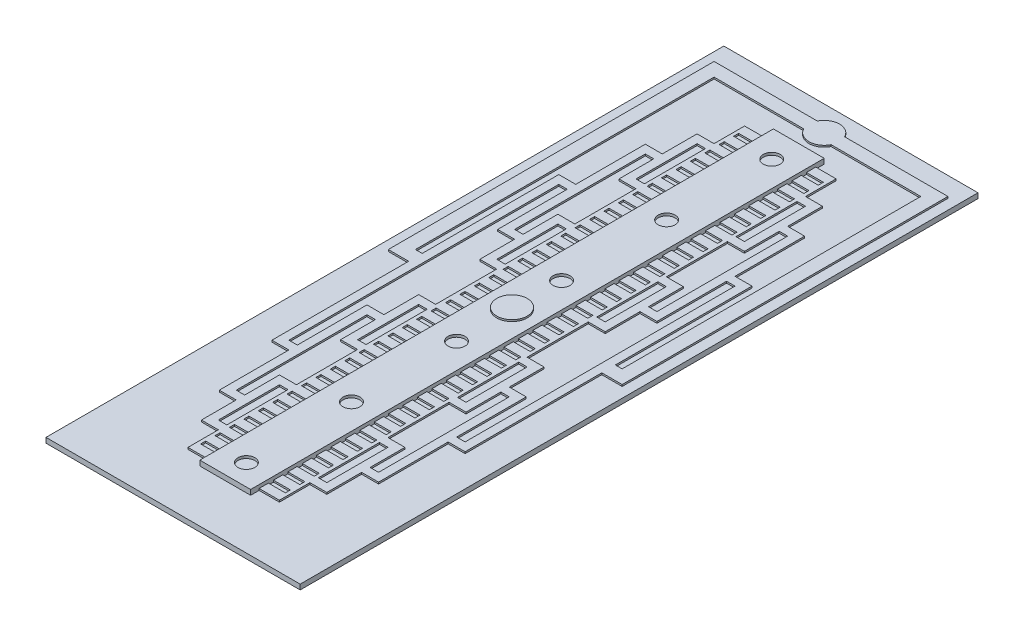
SolidWorks part; units mm, degrees
ref_plane "Front Plane" through (0, 0, 0) normal (0, 0, 1) x (1, 0, 0)
ref_plane "Top Plane" through (0, 0, 0) normal (0, 1, 0) x (1, 0, 0)
ref_plane "Right Plane" through (0, 0, 0) normal (1, 0, 0) x (0, 0, -1)
sketch "Sketch2" plane through (0, 0, 0) normal (0, 1, 0) x (1, 0, 0)
  line L1 (-7.5, 20) -> (7.5, 20)
  line L2 (-7.5, 20) -> (-7.5, -20)
  line L3 (-7.5, -20) -> (7.5, -20)
  line L4 (7.5, 20) -> (7.5, -20)
  line L5 (-7.5, 20) -> (7.5, -20) construction
  line L6 (-7.5, -20) -> (7.5, 20) construction
  point P0 (0, 0)
extrude "Boss-Extrude1" add sketch "Sketch2" along normal blind 0.3
sketch "Sketch3" plane through (0, 0.3, 0) normal (0, 1, 0) x (1, 0, 0)
  line L1 (-1.5, 16.925) -> (1.5, 16.925)
  line L2 (-1.5, 16.925) -> (-1.5, -16.925)
  line L3 (-1.5, -16.925) -> (1.5, -16.925)
  line L4 (1.5, 16.925) -> (1.5, -16.925)
  line L5 (-1.5, 16.925) -> (1.5, -16.925) construction
  line L6 (-1.5, -16.925) -> (1.5, 16.925) construction
  point P0 (0, 0)
extrude "Boss-Extrude2" add sketch "Sketch3" along normal blind 0.3
sketch "Sketch4" plane through (0, 0.3, 0) normal (0, 1, 0) x (1, 0, 0)
  line L0 (0, 19.2283) -> (0, -19.2283) construction
  line L1 (-7.7467, 0) -> (7.7467, 0) construction
  line L2 (1.5, 16.425) -> (2.7, 16.425)
  line L3 (1.5, 16.425) -> (1.5, -16.425)
  line L4 (2.7, 16.425) -> (2.7, -16.425)
  line L5 (1.5, -16.425) -> (2.7, -16.425)
  line L6 (1.5, -16.925) -> (1.5, 16.925) construction
  line L7 (-1.5, -16.425) -> (-2.7, -16.425)
  line L8 (-1.5, 16.425) -> (-1.5, -16.425)
  line L9 (-2.7, 16.425) -> (-2.7, -16.425)
  line L10 (-1.5, 16.425) -> (-2.7, 16.425)
  point P3 (2.7, 0)
  point P4 (0, 0)
  point P8 (0, 0)
extrude "Boss-Extrude3" add sketch "Sketch4" along normal blind 0.1
sketch "Sketch5" plane through (0, 0.4, 0) normal (0, 1, 0) x (1, 0, 0)
  line L0 (1.5, 16.425) -> (1.5, -16.425) construction
  line L1 (1.5, 15.875) -> (2.5, 15.875)
  line L2 (1.5, 15.875) -> (1.5, 15.575)
  line L3 (2.5, 15.875) -> (2.5, 15.575)
  line L4 (1.5, 15.575) -> (2.5, 15.575)
  line L5 (-1.5, 15.875) -> (-1.5, 15.575)
  line L6 (-2.5, 15.875) -> (-1.5, 15.875)
  line L7 (-2.5, 15.875) -> (-2.5, 15.575)
  line L8 (-2.5, 15.575) -> (-1.5, 15.575)
  line L9 (-1.5, 15.025) -> (-1.5, 14.725)
  line L10 (-2.5, 15.025) -> (-1.5, 15.025)
  line L11 (-2.5, 15.025) -> (-2.5, 14.725)
  line L12 (-2.5, 14.725) -> (-1.5, 14.725)
  line L13 (-1.5, 14.175) -> (-1.5, 13.875)
  line L14 (-2.5, 14.175) -> (-1.5, 14.175)
  line L15 (-2.5, 14.175) -> (-2.5, 13.875)
  line L16 (-2.5, 13.875) -> (-1.5, 13.875)
  line L17 (-1.5, 13.325) -> (-1.5, 13.025)
  line L18 (-2.5, 13.325) -> (-1.5, 13.325)
  line L19 (-2.5, 13.325) -> (-2.5, 13.025)
  line L20 (-2.5, 13.025) -> (-1.5, 13.025)
  line L21 (-1.5, 12.475) -> (-1.5, 12.175)
  line L22 (-2.5, 12.475) -> (-1.5, 12.475)
  line L23 (-2.5, 12.475) -> (-2.5, 12.175)
  line L24 (-2.5, 12.175) -> (-1.5, 12.175)
  line L25 (-1.5, 11.625) -> (-1.5, 11.325)
  line L26 (-2.5, 11.625) -> (-1.5, 11.625)
  line L27 (-2.5, 11.625) -> (-2.5, 11.325)
  line L28 (-2.5, 11.325) -> (-1.5, 11.325)
  line L29 (-1.5, 10.775) -> (-1.5, 10.475)
  line L30 (-2.5, 10.775) -> (-1.5, 10.775)
  line L31 (-2.5, 10.775) -> (-2.5, 10.475)
  line L32 (-2.5, 10.475) -> (-1.5, 10.475)
  line L33 (-1.5, 9.925) -> (-1.5, 9.625)
  line L34 (-2.5, 9.925) -> (-1.5, 9.925)
  line L35 (-2.5, 9.925) -> (-2.5, 9.625)
  line L36 (-2.5, 9.625) -> (-1.5, 9.625)
  line L37 (-1.5, 9.075) -> (-1.5, 8.775)
  line L38 (-2.5, 9.075) -> (-1.5, 9.075)
  line L39 (-2.5, 9.075) -> (-2.5, 8.775)
  line L40 (-2.5, 8.775) -> (-1.5, 8.775)
  line L41 (-1.5, 8.225) -> (-1.5, 7.925)
  line L42 (-2.5, 8.225) -> (-1.5, 8.225)
  line L43 (-2.5, 8.225) -> (-2.5, 7.925)
  line L44 (-2.5, 7.925) -> (-1.5, 7.925)
  line L45 (-1.5, 7.375) -> (-1.5, 7.075)
  line L46 (-2.5, 7.375) -> (-1.5, 7.375)
  line L47 (-2.5, 7.375) -> (-2.5, 7.075)
  line L48 (-2.5, 7.075) -> (-1.5, 7.075)
  line L49 (-1.5, 6.525) -> (-1.5, 6.225)
  line L50 (-2.5, 6.525) -> (-1.5, 6.525)
  line L51 (-2.5, 6.525) -> (-2.5, 6.225)
  line L52 (-2.5, 6.225) -> (-1.5, 6.225)
  line L53 (-1.5, 5.675) -> (-1.5, 5.375)
  line L54 (-2.5, 5.675) -> (-1.5, 5.675)
  line L55 (-2.5, 5.675) -> (-2.5, 5.375)
  line L56 (-2.5, 5.375) -> (-1.5, 5.375)
  line L57 (-1.5, 4.825) -> (-1.5, 4.525)
  line L58 (-2.5, 4.825) -> (-1.5, 4.825)
  line L59 (-2.5, 4.825) -> (-2.5, 4.525)
  line L60 (-2.5, 4.525) -> (-1.5, 4.525)
  line L61 (-1.5, 3.975) -> (-1.5, 3.675)
  line L62 (-2.5, 3.975) -> (-1.5, 3.975)
  line L63 (-2.5, 3.975) -> (-2.5, 3.675)
  line L64 (-2.5, 3.675) -> (-1.5, 3.675)
  line L65 (-1.5, 3.125) -> (-1.5, 2.825)
  line L66 (-2.5, 3.125) -> (-1.5, 3.125)
  line L67 (-2.5, 3.125) -> (-2.5, 2.825)
  line L68 (-2.5, 2.825) -> (-1.5, 2.825)
  line L69 (-1.5, 2.275) -> (-1.5, 1.975)
  line L70 (-2.5, 2.275) -> (-1.5, 2.275)
  line L71 (-2.5, 2.275) -> (-2.5, 1.975)
  line L72 (-2.5, 1.975) -> (-1.5, 1.975)
  line L73 (-1.5, 1.425) -> (-1.5, 1.125)
  line L74 (-2.5, 1.425) -> (-1.5, 1.425)
  line L75 (-2.5, 1.425) -> (-2.5, 1.125)
  line L76 (-2.5, 1.125) -> (-1.5, 1.125)
  line L77 (-1.5, 0.575) -> (-1.5, 0.275)
  line L78 (-2.5, 0.575) -> (-1.5, 0.575)
  line L79 (-2.5, 0.575) -> (-2.5, 0.275)
  line L80 (-2.5, 0.275) -> (-1.5, 0.275)
  line L81 (-1.5, -0.275) -> (-1.5, -0.575)
  line L82 (-2.5, -0.275) -> (-1.5, -0.275)
  line L83 (-2.5, -0.275) -> (-2.5, -0.575)
  line L84 (-2.5, -0.575) -> (-1.5, -0.575)
  line L85 (-1.5, -1.125) -> (-1.5, -1.425)
  line L86 (-2.5, -1.125) -> (-1.5, -1.125)
  line L87 (-2.5, -1.125) -> (-2.5, -1.425)
  line L88 (-2.5, -1.425) -> (-1.5, -1.425)
  line L89 (-1.5, -1.975) -> (-1.5, -2.275)
  line L90 (-2.5, -1.975) -> (-1.5, -1.975)
  line L91 (-2.5, -1.975) -> (-2.5, -2.275)
  line L92 (-2.5, -2.275) -> (-1.5, -2.275)
  line L93 (-1.5, -2.825) -> (-1.5, -3.125)
  line L94 (-2.5, -2.825) -> (-1.5, -2.825)
  line L95 (-2.5, -2.825) -> (-2.5, -3.125)
  line L96 (-2.5, -3.125) -> (-1.5, -3.125)
  line L97 (-1.5, -3.675) -> (-1.5, -3.975)
  line L98 (-2.5, -3.675) -> (-1.5, -3.675)
  line L99 (-2.5, -3.675) -> (-2.5, -3.975)
  line L100 (-2.5, -3.975) -> (-1.5, -3.975)
  line L101 (-1.5, -4.525) -> (-1.5, -4.825)
  line L102 (-2.5, -4.525) -> (-1.5, -4.525)
  line L103 (-2.5, -4.525) -> (-2.5, -4.825)
  line L104 (-2.5, -4.825) -> (-1.5, -4.825)
  line L105 (-1.5, -5.375) -> (-1.5, -5.675)
  line L106 (-2.5, -5.375) -> (-1.5, -5.375)
  line L107 (-2.5, -5.375) -> (-2.5, -5.675)
  line L108 (-2.5, -5.675) -> (-1.5, -5.675)
  line L109 (-1.5, -6.225) -> (-1.5, -6.525)
  line L110 (-2.5, -6.225) -> (-1.5, -6.225)
  line L111 (-2.5, -6.225) -> (-2.5, -6.525)
  line L112 (-2.5, -6.525) -> (-1.5, -6.525)
  line L113 (-1.5, -7.075) -> (-1.5, -7.375)
  line L114 (-2.5, -7.075) -> (-1.5, -7.075)
  line L115 (-2.5, -7.075) -> (-2.5, -7.375)
  line L116 (-2.5, -7.375) -> (-1.5, -7.375)
  line L117 (-1.5, -7.925) -> (-1.5, -8.225)
  line L118 (-2.5, -7.925) -> (-1.5, -7.925)
  line L119 (-2.5, -7.925) -> (-2.5, -8.225)
  line L120 (-2.5, -8.225) -> (-1.5, -8.225)
  line L121 (-1.5, -8.775) -> (-1.5, -9.075)
  line L122 (-2.5, -8.775) -> (-1.5, -8.775)
  line L123 (-2.5, -8.775) -> (-2.5, -9.075)
  line L124 (-2.5, -9.075) -> (-1.5, -9.075)
  line L125 (-1.5, -9.625) -> (-1.5, -9.925)
  line L126 (-2.5, -9.625) -> (-1.5, -9.625)
  line L127 (-2.5, -9.625) -> (-2.5, -9.925)
  line L128 (-2.5, -9.925) -> (-1.5, -9.925)
  line L129 (-1.5, -10.475) -> (-1.5, -10.775)
  line L130 (-2.5, -10.475) -> (-1.5, -10.475)
  line L131 (-2.5, -10.475) -> (-2.5, -10.775)
  line L132 (-2.5, -10.775) -> (-1.5, -10.775)
  line L133 (-1.5, -11.325) -> (-1.5, -11.625)
  line L134 (-2.5, -11.325) -> (-1.5, -11.325)
  line L135 (-2.5, -11.325) -> (-2.5, -11.625)
  line L136 (-2.5, -11.625) -> (-1.5, -11.625)
  line L137 (-1.5, -12.175) -> (-1.5, -12.475)
  line L138 (-2.5, -12.175) -> (-1.5, -12.175)
  line L139 (-2.5, -12.175) -> (-2.5, -12.475)
  line L140 (-2.5, -12.475) -> (-1.5, -12.475)
  line L141 (-1.5, -13.025) -> (-1.5, -13.325)
  line L142 (-2.5, -13.025) -> (-1.5, -13.025)
  line L143 (-2.5, -13.025) -> (-2.5, -13.325)
  line L144 (-2.5, -13.325) -> (-1.5, -13.325)
  line L145 (-1.5, -13.875) -> (-1.5, -14.175)
  line L146 (-2.5, -13.875) -> (-1.5, -13.875)
  line L147 (-2.5, -13.875) -> (-2.5, -14.175)
  line L148 (-2.5, -14.175) -> (-1.5, -14.175)
  line L149 (-1.5, -14.725) -> (-1.5, -15.025)
  line L150 (-2.5, -14.725) -> (-1.5, -14.725)
  line L151 (-2.5, -14.725) -> (-2.5, -15.025)
  line L152 (-2.5, -15.025) -> (-1.5, -15.025)
  line L153 (-1.5, -15.575) -> (-1.5, -15.875)
  line L154 (-2.5, -15.575) -> (-1.5, -15.575)
  line L155 (-2.5, -15.575) -> (-2.5, -15.875)
  line L156 (-2.5, -15.875) -> (-1.5, -15.875)
  line L157 (2.5, 15.025) -> (2.5, 14.725)
  line L158 (1.5, 15.025) -> (2.5, 15.025)
  line L159 (1.5, 15.025) -> (1.5, 14.725)
  line L160 (1.5, 14.725) -> (2.5, 14.725)
  line L161 (2.5, 14.175) -> (2.5, 13.875)
  line L162 (1.5, 14.175) -> (2.5, 14.175)
  line L163 (1.5, 14.175) -> (1.5, 13.875)
  line L164 (1.5, 13.875) -> (2.5, 13.875)
  line L165 (2.5, 13.325) -> (2.5, 13.025)
  line L166 (1.5, 13.325) -> (2.5, 13.325)
  line L167 (1.5, 13.325) -> (1.5, 13.025)
  line L168 (1.5, 13.025) -> (2.5, 13.025)
  line L169 (2.5, 12.475) -> (2.5, 12.175)
  line L170 (1.5, 12.475) -> (2.5, 12.475)
  line L171 (1.5, 12.475) -> (1.5, 12.175)
  line L172 (1.5, 12.175) -> (2.5, 12.175)
  line L173 (2.5, 11.625) -> (2.5, 11.325)
  line L174 (1.5, 11.625) -> (2.5, 11.625)
  line L175 (1.5, 11.625) -> (1.5, 11.325)
  line L176 (1.5, 11.325) -> (2.5, 11.325)
  line L177 (2.5, 10.775) -> (2.5, 10.475)
  line L178 (1.5, 10.775) -> (2.5, 10.775)
  line L179 (1.5, 10.775) -> (1.5, 10.475)
  line L180 (1.5, 10.475) -> (2.5, 10.475)
  line L181 (2.5, 9.925) -> (2.5, 9.625)
  line L182 (1.5, 9.925) -> (2.5, 9.925)
  line L183 (1.5, 9.925) -> (1.5, 9.625)
  line L184 (1.5, 9.625) -> (2.5, 9.625)
  line L185 (2.5, 9.075) -> (2.5, 8.775)
  line L186 (1.5, 9.075) -> (2.5, 9.075)
  line L187 (1.5, 9.075) -> (1.5, 8.775)
  line L188 (1.5, 8.775) -> (2.5, 8.775)
  line L189 (2.5, 8.225) -> (2.5, 7.925)
  line L190 (1.5, 8.225) -> (2.5, 8.225)
  line L191 (1.5, 8.225) -> (1.5, 7.925)
  line L192 (1.5, 7.925) -> (2.5, 7.925)
  line L193 (2.5, 7.375) -> (2.5, 7.075)
  line L194 (1.5, 7.375) -> (2.5, 7.375)
  line L195 (1.5, 7.375) -> (1.5, 7.075)
  line L196 (1.5, 7.075) -> (2.5, 7.075)
  line L197 (2.5, 6.525) -> (2.5, 6.225)
  line L198 (1.5, 6.525) -> (2.5, 6.525)
  line L199 (1.5, 6.525) -> (1.5, 6.225)
  line L200 (1.5, 6.225) -> (2.5, 6.225)
  line L201 (2.5, 5.675) -> (2.5, 5.375)
  line L202 (1.5, 5.675) -> (2.5, 5.675)
  line L203 (1.5, 5.675) -> (1.5, 5.375)
  line L204 (1.5, 5.375) -> (2.5, 5.375)
  line L205 (2.5, 4.825) -> (2.5, 4.525)
  line L206 (1.5, 4.825) -> (2.5, 4.825)
  line L207 (1.5, 4.825) -> (1.5, 4.525)
  line L208 (1.5, 4.525) -> (2.5, 4.525)
  line L209 (2.5, 3.975) -> (2.5, 3.675)
  line L210 (1.5, 3.975) -> (2.5, 3.975)
  line L211 (1.5, 3.975) -> (1.5, 3.675)
  line L212 (1.5, 3.675) -> (2.5, 3.675)
  line L213 (2.5, 3.125) -> (2.5, 2.825)
  line L214 (1.5, 3.125) -> (2.5, 3.125)
  line L215 (1.5, 3.125) -> (1.5, 2.825)
  line L216 (1.5, 2.825) -> (2.5, 2.825)
  line L217 (2.5, 2.275) -> (2.5, 1.975)
  line L218 (1.5, 2.275) -> (2.5, 2.275)
  line L219 (1.5, 2.275) -> (1.5, 1.975)
  line L220 (1.5, 1.975) -> (2.5, 1.975)
  line L221 (2.5, 1.425) -> (2.5, 1.125)
  line L222 (1.5, 1.425) -> (2.5, 1.425)
  line L223 (1.5, 1.425) -> (1.5, 1.125)
  line L224 (1.5, 1.125) -> (2.5, 1.125)
  line L225 (2.5, 0.575) -> (2.5, 0.275)
  line L226 (1.5, 0.575) -> (2.5, 0.575)
  line L227 (1.5, 0.575) -> (1.5, 0.275)
  line L228 (1.5, 0.275) -> (2.5, 0.275)
  line L229 (2.5, -0.275) -> (2.5, -0.575)
  line L230 (1.5, -0.275) -> (2.5, -0.275)
  line L231 (1.5, -0.275) -> (1.5, -0.575)
  line L232 (1.5, -0.575) -> (2.5, -0.575)
  line L233 (2.5, -1.125) -> (2.5, -1.425)
  line L234 (1.5, -1.125) -> (2.5, -1.125)
  line L235 (1.5, -1.125) -> (1.5, -1.425)
  line L236 (1.5, -1.425) -> (2.5, -1.425)
  line L237 (2.5, -1.975) -> (2.5, -2.275)
  line L238 (1.5, -1.975) -> (2.5, -1.975)
  line L239 (1.5, -1.975) -> (1.5, -2.275)
  line L240 (1.5, -2.275) -> (2.5, -2.275)
  line L241 (2.5, -2.825) -> (2.5, -3.125)
  line L242 (1.5, -2.825) -> (2.5, -2.825)
  line L243 (1.5, -2.825) -> (1.5, -3.125)
  line L244 (1.5, -3.125) -> (2.5, -3.125)
  line L245 (2.5, -3.675) -> (2.5, -3.975)
  line L246 (1.5, -3.675) -> (2.5, -3.675)
  line L247 (1.5, -3.675) -> (1.5, -3.975)
  line L248 (1.5, -3.975) -> (2.5, -3.975)
  line L249 (2.5, -4.525) -> (2.5, -4.825)
  line L250 (1.5, -4.525) -> (2.5, -4.525)
  line L251 (1.5, -4.525) -> (1.5, -4.825)
  line L252 (1.5, -4.825) -> (2.5, -4.825)
  line L253 (2.5, -5.375) -> (2.5, -5.675)
  line L254 (1.5, -5.375) -> (2.5, -5.375)
  line L255 (1.5, -5.375) -> (1.5, -5.675)
  line L256 (1.5, -5.675) -> (2.5, -5.675)
  line L257 (2.5, -6.225) -> (2.5, -6.525)
  line L258 (1.5, -6.225) -> (2.5, -6.225)
  line L259 (1.5, -6.225) -> (1.5, -6.525)
  line L260 (1.5, -6.525) -> (2.5, -6.525)
  line L261 (2.5, -7.075) -> (2.5, -7.375)
  line L262 (1.5, -7.075) -> (2.5, -7.075)
  line L263 (1.5, -7.075) -> (1.5, -7.375)
  line L264 (1.5, -7.375) -> (2.5, -7.375)
  line L265 (2.5, -7.925) -> (2.5, -8.225)
  line L266 (1.5, -7.925) -> (2.5, -7.925)
  line L267 (1.5, -7.925) -> (1.5, -8.225)
  line L268 (1.5, -8.225) -> (2.5, -8.225)
  line L269 (2.5, -8.775) -> (2.5, -9.075)
  line L270 (1.5, -8.775) -> (2.5, -8.775)
  line L271 (1.5, -8.775) -> (1.5, -9.075)
  line L272 (1.5, -9.075) -> (2.5, -9.075)
  line L273 (2.5, -9.625) -> (2.5, -9.925)
  line L274 (1.5, -9.625) -> (2.5, -9.625)
  line L275 (1.5, -9.625) -> (1.5, -9.925)
  line L276 (1.5, -9.925) -> (2.5, -9.925)
  line L277 (2.5, -10.475) -> (2.5, -10.775)
  line L278 (1.5, -10.475) -> (2.5, -10.475)
  line L279 (1.5, -10.475) -> (1.5, -10.775)
  line L280 (1.5, -10.775) -> (2.5, -10.775)
  line L281 (2.5, -11.325) -> (2.5, -11.625)
  line L282 (1.5, -11.325) -> (2.5, -11.325)
  line L283 (1.5, -11.325) -> (1.5, -11.625)
  line L284 (1.5, -11.625) -> (2.5, -11.625)
  line L285 (2.5, -12.175) -> (2.5, -12.475)
  line L286 (1.5, -12.175) -> (2.5, -12.175)
  line L287 (1.5, -12.175) -> (1.5, -12.475)
  line L288 (1.5, -12.475) -> (2.5, -12.475)
  line L289 (2.5, -13.025) -> (2.5, -13.325)
  line L290 (1.5, -13.025) -> (2.5, -13.025)
  line L291 (1.5, -13.025) -> (1.5, -13.325)
  line L292 (1.5, -13.325) -> (2.5, -13.325)
  line L293 (2.5, -13.875) -> (2.5, -14.175)
  line L294 (1.5, -13.875) -> (2.5, -13.875)
  line L295 (1.5, -13.875) -> (1.5, -14.175)
  line L296 (1.5, -14.175) -> (2.5, -14.175)
  line L297 (2.5, -14.725) -> (2.5, -15.025)
  line L298 (1.5, -14.725) -> (2.5, -14.725)
  line L299 (1.5, -14.725) -> (1.5, -15.025)
  line L300 (1.5, -15.025) -> (2.5, -15.025)
  line L301 (2.5, -15.575) -> (2.5, -15.875)
  line L302 (1.5, -15.575) -> (2.5, -15.575)
  line L303 (1.5, -15.575) -> (1.5, -15.875)
  line L304 (1.5, -15.875) -> (2.5, -15.875)
  point P0 (1.5, 15.875)
  dimension "D1" = 0.55
  dimension "D2" = 2
  dimension "D3" = 38
extrude "Cut-Extrude1" cut sketch "Sketch5" against normal blind 0.1
sketch "Sketch6" plane through (0, 0.3, 0) normal (0, 1, 0) x (1, 0, 0)
  line L0 (-7.9902, 0) -> (7.9902, 0) construction
  line L1 (0, -20.3947) -> (0, 20.3947) construction
  line L2 (1.5, 16.925) -> (-1.5, 16.925) construction
  line L3 (-6.9, 18.825) -> (6.9, 18.825)
  line L4 (-6.1, 18.025) -> (6.1, 18.025)
  line L5 (-6.9, 18.825) -> (-6.9, -0.4)
  line L6 (-6.1, 18.025) -> (-6.1, 0.4)
  line L7 (-6.9, -0.4) -> (-5.7, -0.4)
  line L8 (-6.1, 0.4) -> (-5.7, 0.4)
  line L9 (-2.7, 16.425) -> (-2.7, -16.425) construction
  line L10 (-2.7, 14.6215) -> (-3.7, 14.6215)
  line L11 (-2.7, 14.1215) -> (-3.2, 14.1215)
  line L12 (-2.7, 16.425) -> (-2.7, -16.425) construction
  line L13 (-2.7, 10.0144) -> (-3.7, 10.0144)
  line L14 (-3.7, 12.0679) -> (-3.7, 10.0144)
  line L15 (-3.7, 14.6215) -> (-3.7, 12.5679)
  line L16 (-3.2, 14.1215) -> (-3.2, 10.5144)
  line L17 (-3.2, 10.5144) -> (-2.7, 10.5144)
  line L18 (-2.7, 12.3179) -> (-3.8547, 12.3179) construction
  line L19 (-2.7, 6.4073) -> (-3.7, 6.4073)
  line L20 (-2.7, 5.9073) -> (-3.2, 5.9073)
  line L21 (-2.7, 1.8003) -> (-3.7, 1.8003)
  line L22 (-2.7, 2.3003) -> (-3.2, 2.3003)
  line L23 (-3.2, 2.3003) -> (-3.2, 5.9073)
  line L24 (-3.7, 4.3538) -> (-3.7, 6.4073)
  line L25 (-3.7, 1.8003) -> (-3.7, 3.8538)
  line L26 (-2.7, 4.1038) -> (-3.8547, 4.1038) construction
  line L27 (-2.7, -1.8068) -> (-3.7, -1.8068)
  line L28 (-2.7, -2.3068) -> (-3.2, -2.3068)
  line L29 (-2.7, -6.4139) -> (-3.7, -6.4139)
  line L30 (-3.7, -6.4139) -> (-3.7, -4.3604)
  line L31 (-3.7, -1.8068) -> (-3.7, -3.8604)
  line L32 (-2.7, -5.9139) -> (-3.2, -5.9139)
  line L33 (-3.2, -5.9139) -> (-3.2, -2.3068)
  line L34 (-2.7, -4.1104) -> (-3.9544, -4.1104) construction
  line L35 (-2.7, -10.021) -> (-3.7, -10.021)
  line L36 (-3.7, -10.021) -> (-3.7, -12.0745)
  line L37 (-2.7, -10.521) -> (-3.2, -10.521)
  line L38 (-2.7, -14.628) -> (-3.7, -14.628)
  line L39 (-3.7, -14.628) -> (-3.7, -12.5745)
  line L40 (-2.7, -14.128) -> (-3.2, -14.128)
  line L41 (-3.2, -14.128) -> (-3.2, -10.521)
  line L42 (-2.7, -12.3245) -> (-3.7601, -12.3245) construction
  line L43 (-3.7, 12.5679) -> (-4.7, 12.5679)
  line L44 (-3.7, 12.0679) -> (-4.2, 12.0679)
  line L45 (-4.7, 12.5679) -> (-4.7, 8.4609)
  line L46 (-4.7, 7.9609) -> (-4.7, 3.8538)
  line L47 (-4.7, 3.8538) -> (-3.7, 3.8538)
  line L48 (-3.7, 4.3538) -> (-4.2, 4.3538)
  line L49 (-4.2, 4.3538) -> (-4.2, 12.0679)
  line L50 (-3.7, -3.8604) -> (-4.7, -3.8604)
  line L51 (-4.7, -3.8604) -> (-4.7, -7.9674)
  line L52 (-4.7, -12.5745) -> (-3.7, -12.5745)
  line L53 (-4.7, -12.5745) -> (-4.7, -8.4674)
  line L54 (-3.7, -4.3604) -> (-4.2, -4.3604)
  line L55 (-4.2, -4.3604) -> (-4.2, -12.0745)
  line L56 (-4.2, -12.0745) -> (-3.7, -12.0745)
  line L57 (-2.7, -8.2174) -> (-4.9354, -8.2174) construction
  line L58 (-2.7, 8.2109) -> (-4.9354, 8.2109) construction
  line L59 (-4.7, 8.4609) -> (-5.7, 8.4609)
  line L60 (-5.7, 8.4609) -> (-5.7, 0.4)
  line L61 (-4.7, 7.9609) -> (-5.2, 7.9609)
  line L62 (-5.2, 7.9609) -> (-5.2, -7.9674)
  line L63 (-5.2, -7.9674) -> (-4.7, -7.9674)
  line L64 (-4.7, -8.4674) -> (-5.7, -8.4674)
  line L65 (-5.7, -8.4674) -> (-5.7, -0.4)
  line L66 (2.7, -14.628) -> (3.7, -14.628)
  line L67 (2.7, -14.128) -> (3.2, -14.128)
  line L68 (3.7, -14.628) -> (3.7, -12.5745)
  line L69 (4.7, -12.5745) -> (3.7, -12.5745)
  line L70 (4.2, -12.0745) -> (3.7, -12.0745)
  line L71 (3.2, -14.128) -> (3.2, -10.521)
  line L72 (2.7, -10.521) -> (3.2, -10.521)
  line L73 (3.7, -10.021) -> (3.7, -12.0745)
  line L74 (2.7, -10.021) -> (3.7, -10.021)
  line L75 (4.7, -12.5745) -> (4.7, -8.4674)
  line L76 (4.7, -8.4674) -> (5.7, -8.4674)
  line L77 (5.2, -7.9674) -> (4.7, -7.9674)
  line L78 (2.7, -6.4139) -> (3.7, -6.4139)
  line L79 (2.7, -5.9139) -> (3.2, -5.9139)
  line L80 (3.7, -6.4139) -> (3.7, -4.3604)
  line L81 (4.2, -4.3604) -> (4.2, -12.0745)
  line L82 (3.7, -4.3604) -> (4.2, -4.3604)
  line L83 (4.7, -3.8604) -> (4.7, -7.9674)
  line L84 (3.7, -3.8604) -> (4.7, -3.8604)
  line L85 (3.2, -5.9139) -> (3.2, -2.3068)
  line L86 (2.7, -2.3068) -> (3.2, -2.3068)
  line L87 (3.7, -1.8068) -> (3.7, -3.8604)
  line L88 (2.7, -1.8068) -> (3.7, -1.8068)
  line L89 (5.7, -8.4674) -> (5.7, -0.4)
  line L90 (6.9, -0.4) -> (5.7, -0.4)
  line L91 (6.1, 0.4) -> (5.7, 0.4)
  line L92 (2.7, 1.8003) -> (3.7, 1.8003)
  line L93 (2.7, 2.3003) -> (3.2, 2.3003)
  line L94 (3.7, 1.8003) -> (3.7, 3.8538)
  line L95 (4.7, 3.8538) -> (3.7, 3.8538)
  line L96 (3.7, 4.3538) -> (4.2, 4.3538)
  line L97 (3.2, 2.3003) -> (3.2, 5.9073)
  line L98 (2.7, 5.9073) -> (3.2, 5.9073)
  line L99 (3.7, 4.3538) -> (3.7, 6.4073)
  line L100 (2.7, 6.4073) -> (3.7, 6.4073)
  line L101 (4.7, 7.9609) -> (4.7, 3.8538)
  line L102 (5.2, 7.9609) -> (5.2, -7.9674)
  line L103 (4.7, 7.9609) -> (5.2, 7.9609)
  line L104 (5.7, 8.4609) -> (5.7, 0.4)
  line L105 (4.7, 8.4609) -> (5.7, 8.4609)
  line L106 (2.7, 10.0144) -> (3.7, 10.0144)
  line L107 (3.2, 10.5144) -> (2.7, 10.5144)
  line L108 (3.7, 12.0679) -> (3.7, 10.0144)
  line L109 (4.7, 12.5679) -> (4.7, 8.4609)
  line L110 (4.2, 4.3538) -> (4.2, 12.0679)
  line L111 (3.7, 12.0679) -> (4.2, 12.0679)
  line L112 (3.7, 12.5679) -> (4.7, 12.5679)
  line L113 (3.2, 14.1215) -> (3.2, 10.5144)
  line L114 (2.7, 14.1215) -> (3.2, 14.1215)
  line L115 (3.7, 14.6215) -> (3.7, 12.5679)
  line L116 (2.7, 14.6215) -> (3.7, 14.6215)
  line L117 (6.9, 18.825) -> (6.9, -0.4)
  line L118 (6.1, 18.025) -> (6.1, 0.4)
  circle A0 centre (0, 18.425) radius 0.9
  point P0 (0, 16.925)
  point P3 (-6.9, 0)
  point P4 (0, 0)
  point P8 (0, 0)
  point P9 (0, 18.425)
  point P14 (0, 18.825)
  point P15 (0, 18.025)
  point P19 (0, 18.825)
  point P22 (0, 18.025)
  point P24 (-6.9, 0)
  point P25 (-2.7, 16.425)
  point P27 (-2.7, 14.6215)
  point P28 (-2.7, 14.1215)
  point P29 (-2.7, 15.3982)
  point P32 (-2.7, 14.3715)
  point P33 (-2.7, 13.3447)
  point P34 (-2.7, 12.3179)
  point P35 (-2.7, 11.2912)
  point P36 (-2.7, 10.2644)
  point P37 (-2.7, 9.2376)
  point P38 (-2.7, 8.2109)
  point P39 (-2.7, 7.1841)
  point P40 (-2.7, 6.1573)
  point P41 (-2.7, 5.1306)
  point P42 (-2.7, 4.1038)
  point P43 (-2.7, 3.077)
  point P44 (-2.7, 2.0503)
  point P45 (-2.7, 1.0235)
  point P46 (-2.7, -0.0033)
  point P47 (-2.7, -1.0301)
  point P48 (-2.7, -2.0568)
  point P49 (-2.7, -3.0836)
  point P50 (-2.7, -4.1104)
  point P51 (-2.7, -5.1371)
  point P52 (-2.7, -6.1639)
  point P53 (-2.7, -7.1907)
  point P54 (-2.7, -8.2174)
  point P55 (-2.7, -9.2442)
  point P56 (-2.7, -10.271)
  point P57 (-2.7, -11.2977)
  point P58 (-2.7, -12.3245)
  point P59 (-2.7, -13.3513)
  point P60 (-2.7, -14.378)
  point P61 (-2.7, -15.4048)
  point P62 (-2.7, -16.4316)
  point P69 (-2.7, 10.0144)
  point P70 (-2.7, 10.5144)
  point P81 (-3.508, 12.3179)
  point P82 (-2.7, 5.9073)
  point P83 (-2.7, 6.4073)
  point P88 (-2.7, 1.8003)
  point P89 (-2.7, 2.3003)
  point P98 (-3.5077, 4.1038)
  point P99 (-2.7, -2.3068)
  point P100 (-2.7, -1.8068)
  point P105 (-2.7, -6.4139)
  point P106 (-2.7, -5.9139)
  point P115 (-3.5074, -4.1104)
  point P116 (-2.7, -10.521)
  point P117 (-2.7, -10.021)
  point P123 (-2.7, -14.628)
  point P124 (-2.7, -14.128)
  point P132 (-3.4763, -12.3245)
  point P147 (-4.4672, -8.2174)
  point P150 (-4.47, 8.2109)
  point P215 (-4.7, -8.2174)
  point P216 (-3.7, -12.3245)
  point P217 (-3.7, -4.1104)
  point P218 (-3.7, 4.1038)
  point P219 (-3.7, 12.3179)
  point P220 (-4.7, 8.2109)
  point P222 (-4.7, -7.9674)
  line M97 (-2.7, -16.425) -> (-2.7, 16.425)
  line M103 (2.7, 16.425) -> (2.7, -16.425)
  dimension "D2" = 0.4
  dimension "D1" = 1.5
  dimension "D3" = 0.4
  dimension "D4" = 0.4
  dimension "D5" = 33
  dimension "D6" = 0.25
  dimension "D7" = 0.25
  dimension "D8" = 0.25
  dimension "D9" = 0.25
  dimension ".25" = 0.25
  dimension "D10" = 0.25
  dimension "D11" = 0.25
  dimension "D12" = 0.25
  dimension "D13" = 0.25
  dimension "D14" = 0.25
  dimension "D15" = 0.25
  dimension "D16" = 0.25
  dimension "D17" = 0.25
  dimension "D18" = 0.25
  dimension "D19" = 0.25
  dimension "D20" = 0.25
  dimension "D21" = 0.25
  dimension "D23" = 0.25
  dimension "D24" = 0.25
  dimension "D25" = 0.25
  dimension "D26" = 0.25
  dimension "D27" = 0.25
  dimension "D28" = 0.25
  dimension "D29" = 0.25
  dimension "D30" = 0.25
  dimension "D31" = 0.25
  dimension "D32" = 0.25
extrude "Boss-Extrude4" add sketch "Sketch6" along normal blind 0.1 contours A0 L4 L118 L91 L104 L105 L109 L112 L115 L116 L114 L113 L107 L106 L108 L111 L110 L96 L99 L100 L98 L97 L93 L92 L94 L95 L101 L103 L102 L77 L83 L84 L87 L88 L86 L85 L79 L78 L80 L82 L81 L70 L73 L74 M103 | A0 L3 L5 L7 L65 L64 L53 L52 L39 L38 L40 L41 L37 L35 L36 L56 L55 L54 L30 L29 L32 L33 L28 L27 L31 L50 L51 L63 L62 L61 L46 L47 L25 L21 L22 L23 L20 L19 L24 L48 L49 L44 L14 L13 M97 | L4 A0 L3 | L3 A0 | L4 A0 region at (-3.8531, 0.3, -18.485) region at (0, 0.3, -19.0307) region at (0, 0.3, -18.425) region at (3.8531, 0.3, -18.485) region at (0, 0.3, -17.8193)
sketch "Sketch7" plane through (0, 0.6, 0) normal (0, 1, 0) x (1, 0, 0)
  circle A0 centre (0, 0) radius 0.9
extrude "Boss-Extrude5" add sketch "Sketch7" along normal blind 0.1 contours A0
sketch "Sketch8" plane through (0, 0.6, 0) normal (0, 1, 0) x (1, 0, 0)
  circle A0 centre (0, 15.3265) radius 0.5
  circle A1 centre (0, 9.1265) radius 0.5
  circle A2 centre (0, 2.9265) radius 0.5
  circle A3 centre (0, -3.2735) radius 0.5
  circle A4 centre (0, -9.4735) radius 0.5
  circle A5 centre (0, -15.6735) radius 0.5
  dimension "D1" = 6
extrude "Cut-Extrude2" cut sketch "Sketch8" against normal blind 0.15
